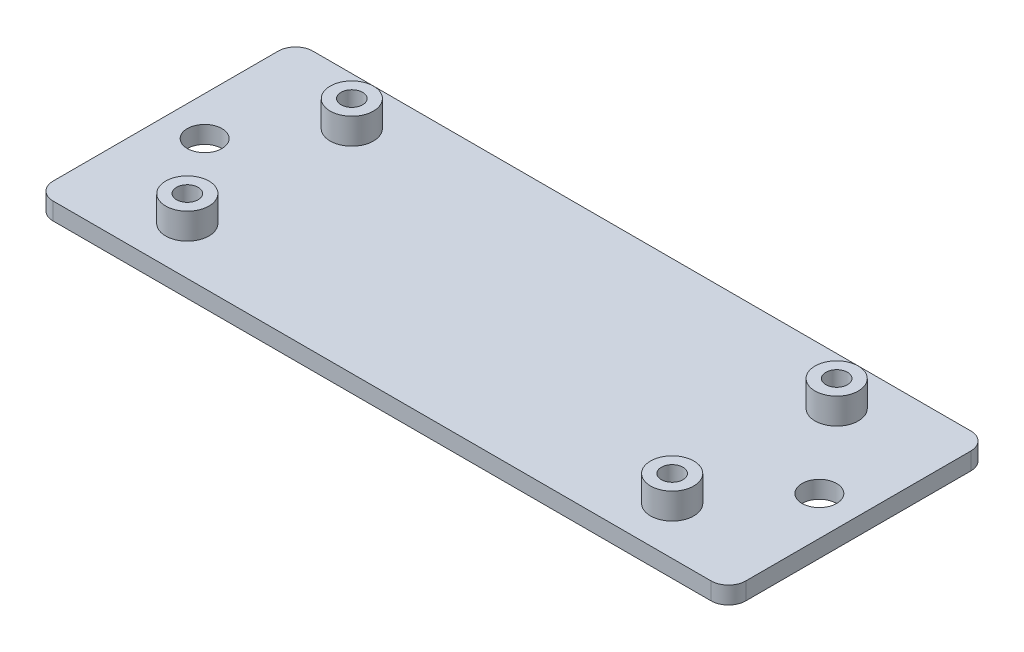
SolidWorks part; units mm, degrees
ref_plane "Спереди" through (0, 0, 0) normal (0, 0, 1) x (1, 0, 0)
ref_plane "Сверху" through (0, 0, 0) normal (0, 1, 0) x (1, 0, 0)
ref_plane "Справа" through (0, 0, 0) normal (1, 0, 0) x (0, 0, -1)
sketch "Эскиз1" plane through (0, 0, 0) normal (0, 1, 0) x (1, 0, 0)
  line L1 (0, 0) -> (80, 0)
  line L2 (0, 0) -> (0, -30)
  line L3 (0, -30) -> (80, -30)
  line L4 (80, 0) -> (80, -30)
  dimension "D1" = 30
  dimension "D2" = 80
extrude "Бобышка-Вытянуть1" add sketch "Эскиз1" along normal blind 2
sketch "Эскиз2" plane through (0, 2, 0) normal (0, 1, 0) x (1, 0, 0)
  line L0 (0, 0) -> (0, -30) construction
  line L1 (80, 0) -> (0, 0) construction
  line L3 (0, -30) -> (80, -30) construction
  line L4 (80, -30) -> (80, 0) construction
  circle A0 centre (12, -5.5) radius 2.5
  circle A1 centre (12, -24.5) radius 2.5
  circle A2 centre (68, -5.5) radius 2.5
  circle A3 centre (68, -24.5) radius 2.5
  point P12 (68.2169, -24.0015)
  dimension "D1" = 12
  dimension "D2" = 5.5
  dimension "D3" = 12
  dimension "D4" = 5.5
  dimension "D5" = 12
  dimension "D6" = 5.5
  dimension "D7" = 12
  dimension "D8" = 5.5
  dimension "D9" = 5
  dimension "D10" = 5
  dimension "D11" = 5
  dimension "D12" = 5
extrude "Бобышка-Вытянуть2" add sketch "Эскиз2" along normal blind 3
sketch "Эскиз3" plane through (0, 5, 0) normal (0, 1, 0) x (1, 0, 0)
  circle A0 centre (12, -5.5) radius 1.25
  circle A1 centre (12, -24.5) radius 1.25
  circle A2 centre (68, -5.5) radius 1.25
  circle A3 centre (68, -24.5) radius 1.25
  dimension "D1" = 2.5
  dimension "D2" = 2.5
  dimension "D3" = 2.5
  dimension "D4" = 2.5
extrude "Вырез-Вытянуть1" cut sketch "Эскиз3" against normal through all both and the other way through all
sketch "Эскиз4" plane through (0, 2, 0) normal (0, 1, 0) x (1, 0, 0)
  line L0 (0, -15) -> (80, -15) construction
  line L1 (0, 0) -> (0, -30) construction
  line L2 (80, -30) -> (80, 0) construction
  circle A0 centre (4.5, -15) radius 2
  circle A1 centre (75.5, -15) radius 2
  dimension "D1" = 4.5
  dimension "D2" = 4
  dimension "D3" = 4.5
  dimension "D4" = 4
extrude "Вырез-Вытянуть2" cut sketch "Эскиз4" against normal through all both and the other way through all
fillet "Скругление1" radius 2 1 edges at (0, 1, 30) type face fillet first side face at (0, 1, 15) second side face at (40, 1, 30)
fillet "Скругление2" radius 2 1 edges at (0, 1, 0) type face fillet first side face at (40, 1, 0) second side face at (0, 1, 14)
fillet "Скругление3" radius 2 1 edges at (80, 1, 0) type face fillet first side face at (41, 1, 0) second side face at (80, 1, 15)
fillet "Скругление4" radius 2 1 edges at (80, 1, 30) type face fillet first side face at (80, 1, 16) second side face at (41, 1, 30)
